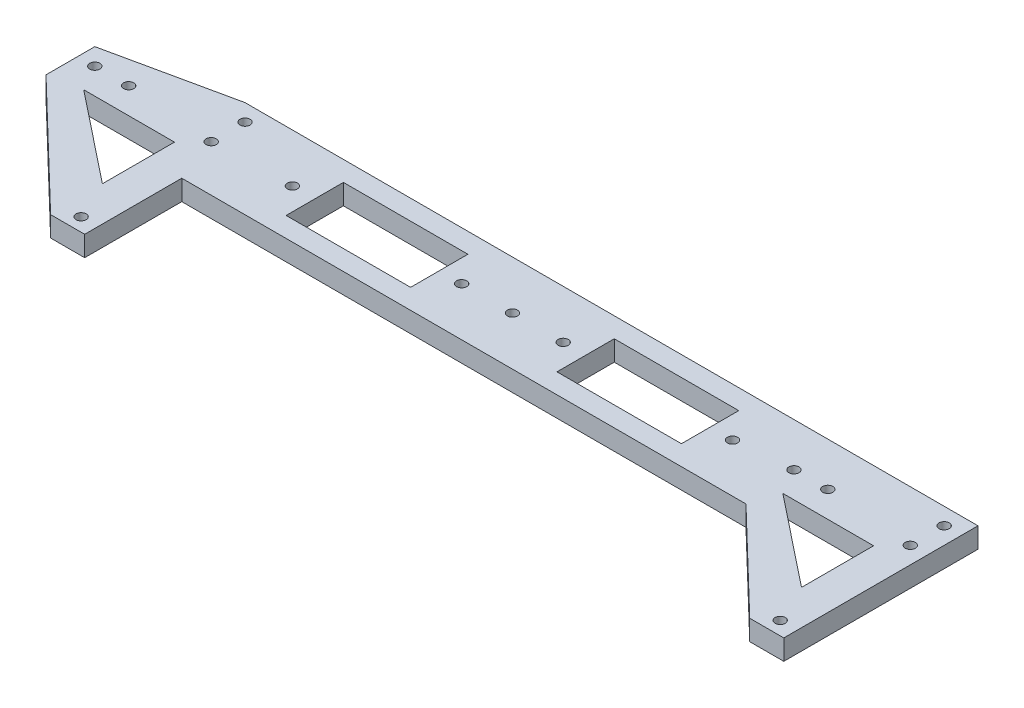
SolidWorks part; units mm, degrees
ref_plane "Front Plane" through (0, 0, 0) normal (0, 0, 1) x (1, 0, 0)
ref_plane "Top Plane" through (0, 0, 0) normal (0, 1, 0) x (1, 0, 0)
ref_plane "Right Plane" through (0, 0, 0) normal (1, 0, 0) x (0, 0, -1)
sketch "Sketch1" plane through (0, 0, 0) normal (0, 1, 0) x (1, 0, 0)
  line L0 (0, 0) -> (0, 10.18) construction
  line L1 (0, 10.18) -> (36.5, 10.18) construction
  line L2 (0, 0) -> (0, 51.73) construction
  line L3 (36.5, 10.18) -> (36.5, 49.6) construction
  line L4 (36.5, 49.6) -> (36.5, 59.6) construction
  line L5 (0, 0) -> (0, -5) construction
  line L7 (0, 51.73) -> (0, 56.73) construction
  line L8 (5, 56.73) -> (-5, 56.73)
  line L9 (-5, 56.73) -> (-5, -5)
  line L10 (5, 56.73) -> (5, 16.6667)
  line L11 (36.5, 59.6) -> (36.5, 64.6) construction
  line L12 (41.5, 64.6) -> (31.5, 64.6)
  line L13 (36.5, 10.18) -> (36.5, -19.82) construction
  line L15 (31.5, 64.6) -> (31.5, 16.6667)
  line L16 (41.5, 64.6) -> (41.5, -19.82)
  line L17 (31.5, 64.6) -> (-5, 56.73)
  line L18 (5, 56.73) -> (31.5, 54.48)
  line L19 (5, 16.6667) -> (31.5, 16.6667)
  line L20 (5, 5.234) -> (31.5, 5.234)
  line L21 (5, 5.234) -> (5, -5)
  line L22 (5, 5.234) -> (-5, 5.234)
  line L23 (-5, 5.234) -> (41.5, 5.234)
  line L24 (31.5, 5.234) -> (31.5, -19.82)
  line L25 (36.5, 10.18) -> (39.514, 10.18) construction
  line L26 (39.514, 10.18) -> (39.514, 11.18) construction
  line L27 (39.514, 11.18) -> (36.5, 11.18) construction
  circle A2 centre (0, 51.73) radius 1.5
  circle A3 centre (36.5, 49.6) radius 1.5
  circle A4 centre (36.5, 59.6) radius 1.5
  circle A5 centre (0, 10.18) radius 1.5
  circle A6 centre (36.5, 11.18) radius 1.5
  dimension "D1" = 10.18
  dimension "D2" = 36.5
  dimension "D3" = 51.73
  dimension "D4" = 39.42
  dimension "D5" = 10
  dimension "D6" = 5
  dimension "D12" = 1
  dimension "D7" = 5
  dimension "D8" = 5
  dimension "D9" = 5
  dimension "D10" = 5
  dimension "D11" = 5
extrude "Boss-Extrude1" add sketch "Sketch1" along normal blind 3 contours L16 L12 L15 A4 A3 | L8 L18 L15 L17 | L10 L8 L9 A2 A5 | L10 L15 region at (4.2459, 0, -36.6984) region at (18.1224, 0, -36.1413) region at (19.9063, 0, -58.7735)
sketch "Sketch4" plane through (0, 3, 0) normal (0, 1, 0) x (1, 0, 0)
  line L0 (0, 51.73) -> (10, 51.73) construction
  circle A0 centre (10, 51.73) radius 1.5
extrude "Cut-Extrude2" cut sketch "Sketch4" against normal blind 7
sketch "Sketch5" plane through (0, 3, 0) normal (0, 1, 0) x (1, 0, 0)
  line L0 (-5, 5.234) -> (-5, 7.234) construction
  line L1 (-5, 56.73) -> (-5, 5.234) construction
  line L3 (-5, 7.234) -> (41.5, 7.234)
  line L4 (-5, 7.234) -> (-5, 5.234)
  line L5 (-5, 5.234) -> (41.5, 5.234)
  line L6 (41.5, 7.234) -> (41.5, 5.234)
  dimension "D1" = 2
extrude "Cut-Extrude3" cut sketch "Sketch5" against normal blind 7
sketch "Sketch6" plane through (0, 3, 0) normal (0, 1, 0) x (1, 0, 0)
  line L0 (31.4436, 7.234) -> (-5, 42.3128)
  line L1 (41.5, 7.234) -> (-5, 7.234) construction
  line L2 (-5, 56.73) -> (-5, 7.234) construction
  line L3 (-5, 42.3128) -> (-5, 7.234)
  line L4 (-5, 7.234) -> (31.4436, 7.234)
extrude "Cut-Extrude4" cut sketch "Sketch6" against normal blind 7
sketch "Sketch7" plane through (0, 3, 0) normal (0, 1, 0) x (1, 0, 0)
  line L0 (31.1931, 22.7729) -> (31.1931, 44.0664)
  line L1 (31.1931, 44.0664) -> (4.3883, 44.0664)
  line L2 (4.3883, 44.0664) -> (31.1931, 22.7729)
extrude "Cut-Extrude5" cut sketch "Sketch7" against normal blind 7
sketch "Sketch8" plane through (0, 3, 0) normal (0, 1, 0) x (1, 0, 0)
  line L0 (41.5, 64.6) -> (31.5, 64.6)
  line L1 (31.5, 64.6) -> (-5, 56.73)
  line L2 (31.5, 64.6) -> (-5, 56.73) construction
  line L3 (-5, 56.73) -> (-5, 42.3128)
  line L4 (-5, 42.3128) -> (31.4436, 7.234)
  line L5 (31.4436, 7.234) -> (41.5, 7.234)
  line L6 (41.5, 64.6) -> (41.5, 7.234) construction
  line L7 (41.5, 7.234) -> (41.5, 64.6)
  line L8 (4.3883, 44.0664) -> (31.1931, 44.0664)
  line L9 (31.1931, 44.0664) -> (31.1931, 22.7729)
  line L10 (31.1931, 22.7729) -> (4.3883, 44.0664)
  line L11 (41.5, 35.917) -> (201.5, 35.917) construction
  line L12 (201.5, 35.917) -> (201.5, 86.7417) construction
  line L13 (248, 64.6) -> (238, 64.6)
  line L14 (238, 64.6) -> (201.5, 56.73)
  line L15 (201.5, 56.73) -> (201.5, 42.3128)
  line L16 (201.5, 42.3128) -> (237.9436, 7.234)
  line L17 (237.9436, 7.234) -> (248, 7.234)
  line L18 (248, 7.234) -> (248, 64.6)
  line L19 (210.8883, 44.0664) -> (237.6931, 44.0664)
  line L20 (237.6931, 44.0664) -> (237.6931, 22.7729)
  line L21 (237.6931, 22.7729) -> (210.8883, 44.0664)
  line L22 (41.5, 64.6) -> (248, 64.6)
  line L23 (41.5, 35.917) -> (208.1446, 35.917)
  circle A0 centre (0, 51.73) radius 1.5
  circle A1 centre (10, 51.73) radius 1.5
  circle A2 centre (36.5, 49.6) radius 1.5
  circle A3 centre (36.5, 59.6) radius 1.5
  circle A4 centre (36.5, 11.18) radius 1.5
  circle A5 centre (206.5, 51.73) radius 1.5
  circle A6 centre (216.5, 51.73) radius 1.5
  circle A7 centre (243, 49.6) radius 1.5
  circle A8 centre (243, 59.6) radius 1.5
  circle A9 centre (243, 11.18) radius 1.5
  line M30 (31.1931, 22.7729) -> (4.3883, 44.0664)
  line M31 (4.3883, 44.0664) -> (31.1931, 44.0664)
  line M32 (31.1931, 44.0664) -> (31.1931, 22.7729)
  line M33 (-5, 42.3128) -> (31.4436, 7.234)
  line M34 (31.4436, 7.234) -> (41.5, 7.234)
  line M35 (41.5, 7.234) -> (41.5, 64.6)
  line M36 (41.5, 64.6) -> (31.5, 64.6)
  line M37 (31.5, 64.6) -> (-5, 56.73)
  line M38 (-5, 56.73) -> (-5, 42.3128)
  circle M39 centre (10, 51.73) radius 1.5
  circle M40 centre (36.5, 11.18) radius 1.5
  circle M41 centre (36.5, 59.6) radius 1.5
  circle M42 centre (36.5, 49.6) radius 1.5
  circle M43 centre (0, 51.73) radius 1.5
  dimension "D1" = 160
  dimension "D2" = 2
extrude "Boss-Extrude2" add sketch "Sketch8" against normal blind 6 contours L7 L23 L16 L15 L14 L22 | L17 L18 L13 L14 L15 L16 A9 A8 A7 A6 A5 L20 L21 L19 | L7 M38 M33 M34 M35 M36 M37 M39 M41 M43 M42 M40 M32 M30 M31 region at (40.7615, 3, -50.2585) region at (124.6519, 3, -50.558) region at (243, 3, -63.8615)
sketch "Sketch9" plane through (0, 3, 0) normal (0, 1, 0) x (1, 0, 0)
  line L0 (124.8223, 35.917) -> (124.8223, 64.6) construction
  line L1 (41.5, 35.917) -> (208.1446, 35.917) construction
  line L2 (248, 64.6) -> (31.5, 64.6) construction
  line L3 (124.8223, 50.2585) -> (59.8223, 50.2585) construction
  circle A0 centre (59.8223, 50.2585) radius 1.5
  circle A1 centre (189.8223, 50.2585) radius 1.5
  circle A2 centre (124.8223, 50.2585) radius 1.5
  dimension "D1" = 65
extrude "Cut-Extrude6" cut sketch "Sketch9" against normal blind 6
sketch "Sketch10" plane through (0, 3, 0) normal (0, 1, 0) x (1, 0, 0)
  line L0 (124.8223, 50.2585) -> (109.8223, 50.2585) construction
  line L1 (124.8223, 50.2585) -> (139.8223, 50.2585) construction
  circle A0 centre (124.8223, 50.2585) radius 1.5
  circle A1 centre (109.8223, 50.2585) radius 1.5
  circle A2 centre (139.8223, 50.2585) radius 1.5
  dimension "D2" = 15
  dimension "D1" = 15
extrude "Cut-Extrude7" cut sketch "Sketch10" against normal blind 6
sketch "Sketch11" plane through (0, 3, 0) normal (0, 1, 0) x (1, 0, 0)
  line L0 (59.8223, 50.2585) -> (109.8223, 50.2585) construction
  line L1 (124.8223, 50.2585) -> (124.8223, 64.6) construction
  line L2 (66.4377, 41.7958) -> (103.2069, 41.7958)
  line L3 (66.4377, 41.7958) -> (66.4377, 58.7212)
  line L4 (66.4377, 58.7212) -> (103.2069, 58.7212)
  line L5 (103.2069, 41.7958) -> (103.2069, 58.7212)
  line L6 (66.4377, 41.7958) -> (103.2069, 58.7212) construction
  line L7 (66.4377, 58.7212) -> (103.2069, 41.7958) construction
  line L8 (248, 64.6) -> (31.5, 64.6) construction
  line L9 (183.2069, 58.7212) -> (146.4377, 58.7212)
  line L10 (146.4377, 41.7958) -> (146.4377, 58.7212)
  line L11 (183.2069, 41.7958) -> (146.4377, 41.7958)
  line L12 (183.2069, 41.7958) -> (183.2069, 58.7212)
  point P4 (84.8223, 50.2585)
extrude "Cut-Extrude8" cut sketch "Sketch11" against normal blind 14 contours L3 L2 L5 L4 | L9 L10 L11 L12
